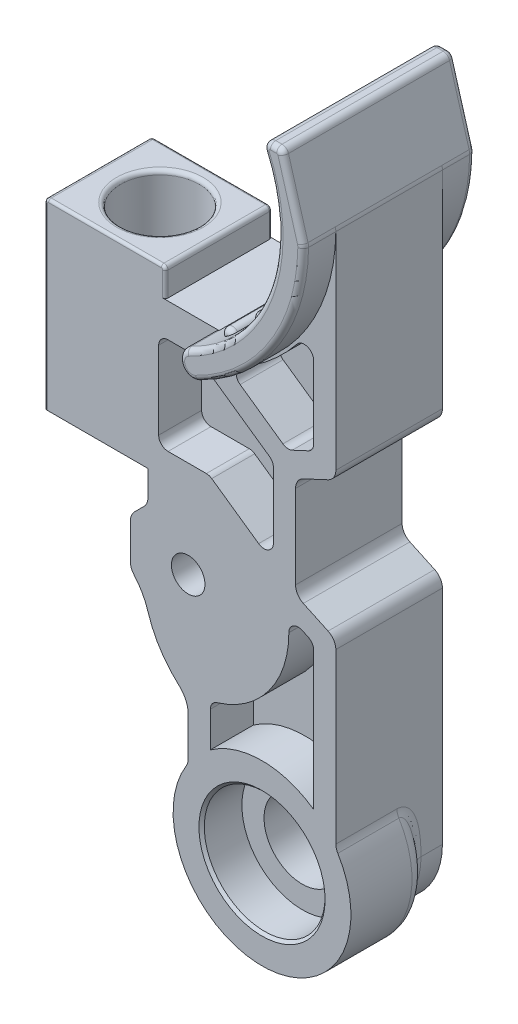
SolidWorks part; units mm, degrees
material "ABS"
ref_plane "Спереди" through (0, 0, 0) normal (0, 0, 1) x (1, 0, 0)
ref_plane "Сверху" through (0, 0, 0) normal (0, 1, 0) x (1, 0, 0)
ref_plane "Справа" through (0, 0, 0) normal (1, 0, 0) x (0, 0, -1)
sketch "Эскиз1" plane through (0, 0, 0) normal (0, 0, 1) x (1, 0, 0)
  line L0 (-9.8, 17.625) -> (-9.8, 14.125)
  line L1 (-5.5, 3.6933) -> (5.5, 3.6933) construction
  line L2 (-5.5, 3.6933) -> (-5.5, 17.1761) construction
  line L3 (-5.5, 17.1761) -> (5.5, 17.1761) construction
  line L4 (5.5, 3.6933) -> (5.5, 17.1761)
  line L5 (-9.8, 17.625) -> (-8.5, 18.925)
  line L6 (-8.5, 18.925) -> (-8.5, 21.225)
  line L7 (-8.5, 21.225) -> (-16.2, 21.225)
  line L8 (-16.2, 21.225) -> (-16.2, 34.875)
  line L9 (-16.2, 34.875) -> (-7.2, 34.875)
  line L10 (-7.2, 34.875) -> (-7.2, 32.775)
  line L11 (-7.2, 32.775) -> (-3.2, 32.775)
  line L12 (2.2662, 49.175) -> (3.9, 49.175)
  line L13 (5.5, 43.6525) -> (5.5, 27.4739)
  line L14 (5.5, 27.4739) -> (2.5, 26.075)
  line L15 (2.5, 26.075) -> (2.5, 18.575)
  line L16 (2.5, 18.575) -> (5.5, 17.1761)
  line L17 (3.9, 49.175) -> (5.5, 43.6525)
  line L18 (-5.5, 3.6933) -> (-5.5, 6.875)
  arc A0 (-5.5, 3.6933) -> (5.5, 3.6933) centre (0, 0) ccw
  arc A1 (-9.8, 14.125) -> (-8.5, 12.0004) centre (-13.2805, 10.5353) cw
  arc A2 (-8.5, 12.0004) -> (-6.1702, 8.3689) centre (-0.8511, 14.3444) ccw
  arc A3 (-6.1702, 8.3689) -> (-5.5, 6.875) centre (-7.5, 6.875) cw
  arc A4 (-3.2, 32.775) -> (2.2662, 49.175) centre (-8.5, 43.6525) ccw
  arc A5 (5.5, 43.6525) -> (-3.2, 30.6945) centre (-8.5, 43.6525) cw construction
  point P3 (-5.5, 15.875)
  point P15 (-9.8, 15.875)
  dimension "D1" = 13.25
  dimension "D2" = 22.5
  dimension "D6" = 2
  dimension "D7" = 8
  dimension "D8" = 5
  dimension "D9" = 13.5
  dimension "D17" = 41.5
  dimension "D22" = 14
  dimension "D23" = 1.9
  dimension "D26" = 25.2
  dimension "D3" = 11
  dimension "D4" = 15.3
  dimension "D5" = 3.5
  dimension "D10" = 14
  dimension "D11" = 45
  dimension "D12" = 11
  dimension "D13" = 3
  dimension "D14" = 2.3
  dimension "D15" = 18.7
  dimension "D16" = 13.65
  dimension "D18" = 4
  dimension "D19" = 2.1
  dimension "D20" = 9
  dimension "D21" = 55.8
  dimension "D24" = 1.6
  dimension "D25" = 7.5
  dimension "D27" = 25
  dimension "D28" = 25
extrude "Бобышка-Вытянуть1" add sketch "Эскиз1" along normal mid plane 7.94
sketch "Эскиз2" plane through (0, 0, 3.97) normal (0, 0, 1) x (1, 0, 0)
  line L0 (-3.85, 5.3915) -> (-3.85, 8.5588)
  line L1 (3.85, 5.3915) -> (3.85, 16.1249)
  line L2 (3.85, 16.1249) -> (2, 16.9876)
  line L3 (2, 16.9876) -> (2, 15.875)
  line L4 (2.5, 18.575) -> (5.5, 17.1761) construction
  line L5 (5.5, 3.6933) -> (5.5, 17.1761) construction
  line L6 (-5.5, 3.6933) -> (-5.5, 6.875) construction
  line L7 (-7.7, 23.075) -> (-7.7, 30.275)
  line L8 (-7.7, 30.275) -> (-4.7947, 30.275)
  line L9 (-4.7947, 30.275) -> (0.85, 26.3225)
  line L10 (0.85, 26.3225) -> (0.85, 19.7303)
  line L11 (0.85, 19.7303) -> (-3.9267, 23.075)
  line L12 (-3.9267, 23.075) -> (-7.7, 23.075)
  line L13 (-16.2, 21.225) -> (-16.2, 34.875) construction
  line L14 (2.5, 26.075) -> (2.5, 18.575) construction
  line L15 (-7.2, 32.775) -> (-3.2, 32.775) construction
  line L16 (-5.5, 17.1761) -> (5.5, 17.1761) construction
  line L18 (-2.5859, 30.7427) -> (1.8878, 27.6101)
  line L19 (1.8878, 27.6101) -> (3.85, 28.5251)
  line L20 (3.85, 28.5251) -> (3.85, 36.6441)
  line L21 (5.5, 43.6525) -> (5.5, 27.4739) construction
  line L22 (5.5, 27.4739) -> (2.5, 26.075) construction
  circle A0 centre (0, 0) radius 4.5
  arc A2 (2, 15.875) -> (-3.85, 8.5588) centre (-5.5, 15.875) cw
  arc A3 (-3.85, 5.3915) -> (3.85, 5.3915) centre (0, 0) cw
  arc A4 (-5.5, 3.6933) -> (5.5, 3.6933) centre (0, 0) ccw construction
  arc A5 (3.85, 36.6441) -> (-2.5859, 30.7427) centre (-8.5, 43.6525) cw
  point P21 (4, 17.8755)
  dimension "D1" = 9
  dimension "D2" = 7.5
  dimension "D15" = 14.2
  dimension "D3" = 1.65
  dimension "D4" = 1.65
  dimension "D5" = 1.65
  dimension "D6" = 8.5
  dimension "D7" = 1.65
  dimension "D8" = 2.5
  dimension "D9" = 35
  dimension "D10" = 5.4
  dimension "D11" = 29.7
  dimension "D12" = 1.65
  dimension "D13" = 1.65
  dimension "D14" = 1.65
extrude "Вырез-Вытянуть1" cut sketch "Эскиз2" against normal blind 3.2
fillet "Скругление1" radius 0.7 13 edges at (2, 16.9876, 2.37) (3.85, 36.6441, 2.37) (-2.5859, 30.7427, 2.37) (1.8878, 27.6101, 2.37) (3.85, 28.5251, 2.37) (-7.7, 30.275, 2.37) (-4.7947, 30.275, 2.37) (0.85, 26.3225, 2.37) (0.85, 19.7303, 2.37) (-3.9267, 23.075, 2.37) (-7.7, 23.075, 2.37) (3.85, 16.1249, 2.37) (-3.85, 8.5588, 2.37)
sketch "Эскиз4" plane through (0, 0, -3.97) normal (0, 0, -1) x (-1, 0, 0)
  line L0 (-3.4458, 16.3134) -> (-2.9958, 16.5232) construction
  line L1 (-2, 15.8888) -> (-2, 15.875) construction
  line L2 (3.85, 8.019) -> (3.85, 5.3915) construction
  line L3 (-3.85, 5.3915) -> (-3.85, 15.679) construction
  line L4 (5.0154, 30.275) -> (7, 30.275) construction
  line L5 (7.7, 29.575) -> (7.7, 23.775) construction
  line L6 (7, 23.075) -> (4.1474, 23.075) construction
  line L7 (3.7459, 22.9484) -> (0.2515, 20.5016) construction
  line L8 (-0.85, 21.075) -> (-0.85, 25.9581) construction
  line L9 (-0.5515, 26.5315) -> (4.6139, 30.1484) construction
  line L10 (-3.85, 28.971) -> (-3.85, 34.3634) construction
  line L11 (1.6305, 30.0736) -> (-1.5568, 27.8419) construction
  line L12 (-2.2541, 27.7809) -> (-3.4458, 28.3366) construction
  line L13 (-3.4458, 16.3134) -> (-2.9958, 16.5232)
  line L14 (-2, 15.8888) -> (-2, 15.875)
  line L15 (3.85, 8.019) -> (3.85, 3.2833)
  line L16 (-3.85, 3.2833) -> (-3.85, 15.679)
  line L17 (5.0154, 30.275) -> (7, 30.275)
  line L18 (7.7, 29.575) -> (7.7, 23.775)
  line L19 (7, 23.075) -> (4.1474, 23.075)
  line L20 (3.7459, 22.9484) -> (0.2515, 20.5016)
  line L21 (-0.85, 21.075) -> (-0.85, 25.9581)
  line L22 (-0.5515, 26.5315) -> (4.6139, 30.1484)
  line L23 (-3.85, 28.971) -> (-3.85, 34.3634)
  line L24 (1.6305, 30.0736) -> (-1.5568, 27.8419)
  line L25 (-2.2541, 27.7809) -> (-3.4458, 28.3366)
  arc A0 (-2, 15.8888) -> (-2.9958, 16.5232) centre (-2.7, 15.8888) ccw construction
  arc A1 (-2, 15.875) -> (3.3506, 8.6896) centre (5.5, 15.875) ccw construction
  arc A2 (3.85, 8.019) -> (3.3506, 8.6896) centre (3.15, 8.019) ccw construction
  arc A4 (-3.4458, 16.3134) -> (-3.85, 15.679) centre (-3.15, 15.679) ccw construction
  arc A5 (7.7, 29.575) -> (7, 30.275) centre (7, 29.575) ccw construction
  arc A6 (7, 23.075) -> (7.7, 23.775) centre (7, 23.775) ccw construction
  arc A7 (4.1474, 23.075) -> (3.7459, 22.9484) centre (4.1474, 22.375) ccw construction
  arc A8 (-0.85, 21.075) -> (0.2515, 20.5016) centre (-0.15, 21.075) ccw construction
  arc A9 (-0.5515, 26.5315) -> (-0.85, 25.9581) centre (-0.15, 25.9581) ccw construction
  arc A10 (5.0154, 30.275) -> (4.6139, 30.1484) centre (5.0154, 29.575) ccw construction
  arc A11 (-2.6027, 34.7998) -> (-3.85, 34.3634) centre (-3.15, 34.3634) ccw construction
  arc A12 (-2.6027, 34.7998) -> (1.5705, 31.258) centre (8.5, 43.6525) ccw construction
  arc A13 (1.6305, 30.0736) -> (1.5705, 31.258) centre (1.229, 30.647) ccw construction
  arc A14 (-2.2541, 27.7809) -> (-1.5568, 27.8419) centre (-1.9583, 28.4153) ccw construction
  arc A15 (-3.85, 28.971) -> (-3.4458, 28.3366) centre (-3.15, 28.971) ccw construction
  arc A16 (-2, 15.8888) -> (-2.9958, 16.5232) centre (-2.7, 15.8888) ccw
  arc A17 (-2, 15.875) -> (3.3506, 8.6896) centre (5.5, 15.875) ccw
  arc A18 (3.85, 8.019) -> (3.3506, 8.6896) centre (3.15, 8.019) ccw
  arc A19 (2.6654, 2.7782) -> (-2.6654, 2.7782) centre (0, 0) ccw
  arc A20 (-3.4458, 16.3134) -> (-3.85, 15.679) centre (-3.15, 15.679) ccw
  arc A21 (7.7, 29.575) -> (7, 30.275) centre (7, 29.575) ccw
  arc A22 (7, 23.075) -> (7.7, 23.775) centre (7, 23.775) ccw
  arc A23 (4.1474, 23.075) -> (3.7459, 22.9484) centre (4.1474, 22.375) ccw
  arc A24 (-0.85, 21.075) -> (0.2515, 20.5016) centre (-0.15, 21.075) ccw
  arc A25 (-0.5515, 26.5315) -> (-0.85, 25.9581) centre (-0.15, 25.9581) ccw
  arc A26 (5.0154, 30.275) -> (4.6139, 30.1484) centre (5.0154, 29.575) ccw
  arc A27 (-2.6027, 34.7998) -> (-3.85, 34.3634) centre (-3.15, 34.3634) ccw
  arc A28 (-2.6027, 34.7998) -> (1.5705, 31.258) centre (8.5, 43.6525) ccw
  arc A29 (1.6305, 30.0736) -> (1.5705, 31.258) centre (1.229, 30.647) ccw
  arc A30 (-2.2541, 27.7809) -> (-1.5568, 27.8419) centre (-1.9583, 28.4153) ccw
  arc A31 (-3.85, 28.971) -> (-3.4458, 28.3366) centre (-3.15, 28.971) ccw
  arc A32 (3.85, 3.2833) -> (2.6654, 2.7782) centre (3.15, 3.2833) cw
  arc A33 (-2.6654, 2.7782) -> (-3.85, 3.2833) centre (-3.15, 3.2833) cw
  dimension "D1" = 3.85
  dimension "D2" = 0.7
extrude "Вырез-Вытянуть2" cut sketch "Эскиз4" against normal blind 3.2
sketch "Эскиз5" plane through (0, 0, 0.77) normal (0, 0, 1) x (1, 0, 0)
  circle A1 centre (0, 0) radius 4.5
  circle A2 centre (0, 0) radius 4.5
  dimension "D1" = 0
extrude "Бобышка-Вытянуть2" add sketch "Эскиз5" along normal blind 0.2
sketch "Эскиз6" plane through (0, 0, 0.97) normal (0, 0, 1) x (1, 0, 0)
  circle A0 centre (0, 0) radius 2.85
  dimension "D1" = 5.7
extrude "Вырез-Вытянуть3" cut sketch "Эскиз6" against normal through all
sketch "Эскиз7" plane through (0, 0, -0.77) normal (0, 0, -1) x (-1, 0, 0)
  line L0 (3.85, 5.3915) -> (3.85, 8.5588) construction
  line L7 (-3.85, 15.679) -> (-3.85, 3.2833)
  line L8 (3.85, 3.2833) -> (3.85, 8.019)
  line L9 (-2, 15.875) -> (-2, 15.8888)
  line L10 (-2.9958, 16.5232) -> (-3.4458, 16.3134)
  line L11 (-3.85, 5.3915) -> (-3.85, 3.2833)
  line L12 (3.85, 3.2833) -> (3.85, 5.3915)
  arc A0 (-3.85, 5.3915) -> (3.85, 5.3915) centre (0, 0) cw
  arc A9 (-3.4458, 16.3134) -> (-3.85, 15.679) centre (-3.15, 15.679) ccw
  arc A10 (-3.85, 3.2833) -> (-2.6654, 2.7782) centre (-3.15, 3.2833) ccw
  arc A11 (2.6654, 2.7782) -> (-2.6654, 2.7782) centre (0, 0) ccw
  arc A12 (2.6654, 2.7782) -> (3.85, 3.2833) centre (3.15, 3.2833) ccw
  arc A13 (3.85, 8.019) -> (3.3506, 8.6896) centre (3.15, 8.019) ccw
  arc A14 (-2, 15.875) -> (3.3506, 8.6896) centre (5.5, 15.875) ccw
  arc A15 (-2, 15.8888) -> (-2.9958, 16.5232) centre (-2.7, 15.8888) ccw
  arc A17 (-3.85, 3.2833) -> (-2.6654, 2.7782) centre (-3.15, 3.2833) ccw
  arc A18 (2.6654, 2.7782) -> (-2.6654, 2.7782) centre (0, 0) ccw
  arc A19 (2.6654, 2.7782) -> (3.85, 3.2833) centre (3.15, 3.2833) ccw
  dimension "D1" = 0
extrude "Бобышка-Вытянуть3" add sketch "Эскиз7" along normal offset from surface (0.9 mm away) 2.3 up to face at (2.85, 0, -3.97)
fillet "Скругление2" radius 0.5 1 edges at (0, 6.625, -1.67)
fillet "Скругление3" radius 0.5 1 edges at (0, 6.625, -0.77)
sketch "Эскиз8" plane through (0, 0, -3.97) normal (0, 0, -1) x (-1, 0, 0)
  line L0 (-5.5, 3.6933) -> (-5.5, 0)
  line L1 (5.5, 0) -> (5.5, 3.6933)
  arc A0 (-5.5, 0) -> (5.5, 0) centre (0, 0) ccw
  arc A3 (-5.5, 3.6933) -> (5.5, 3.6933) centre (0, 0) ccw
  arc A4 (-5.5, 3.6933) -> (5.5, 3.6933) centre (0, 0) ccw
  dimension "D1" = 0
extrude "Вырез-Вытянуть4" cut sketch "Эскиз8" against normal offset from surface (2.39 mm away) 5.55 up to face at (4.5, 0, 3.97)
fillet "Скругление4" radius 1 1 edges at (0, -6.625, -1.58)
sketch "Эскиз9" plane through (0, 0, 0) normal (0, 0, 1) x (1, 0, 0)
  line L3 (-9.8, 17.625) -> (-9.8, 14.125) construction
  line L4 (-5.5, 10.675) -> (-7.9599, 10.675)
  line L5 (-5.5, 21.075) -> (-8.5, 21.075)
  line L6 (-8.5, 18.925) -> (-8.5, 21.225) construction
  line L19 (-9.8, 17.625) -> (-9.8, 14.125)
  line L20 (-8.5, 18.925) -> (-9.8, 17.625)
  line L21 (-8.5, 21.225) -> (-8.5, 18.925)
  line L22 (-9.8, 17.625) -> (-9.8, 14.125)
  line L23 (-8.5, 18.925) -> (-9.8, 17.625)
  line L24 (-8.5, 21.075) -> (-8.5, 18.925)
  arc A0 (-5.5, 10.675) -> (-5.5, 21.075) centre (-5.5, 15.875) ccw
  arc A1 (-8.5, 12.0004) -> (-6.1702, 8.3689) centre (-0.8511, 14.3444) ccw construction
  arc A7 (-8.5, 12.0004) -> (-6.1702, 8.3689) centre (-0.8511, 14.3444) ccw
  arc A8 (-8.5, 12.0004) -> (-9.8, 14.125) centre (-13.2805, 10.5353) ccw
  arc A9 (-8.5, 12.0004) -> (-7.9599, 10.675) centre (-0.8511, 14.3444) ccw
  arc A10 (-8.5, 12.0004) -> (-9.8, 14.125) centre (-13.2805, 10.5353) ccw
  dimension "D1" = 9.5
  dimension "D2" = 0
extrude "Вырез-Вытянуть5" cut sketch "Эскиз9" against normal mid plane 4.35
sketch "Эскиз10" plane through (0, 0, 0) normal (0, 0, 1) x (1, 0, 0)
  line L0 (-8.5, 43.6525) -> (-8.5, 34.875) construction
  line L1 (-16.2, 34.875) -> (-7.2, 34.875) construction
  line L2 (-8.5, 43.6525) -> (-1.5597, 33.7408) construction
  line L3 (-8.5, 43.6525) -> (-1.5597, 33.7408) construction
  line L4 (-8.5, 43.6525) -> (0.7691, 35.8748) construction
  arc A0 (-1.9331, 33.4895) -> (-1.1959, 34.0057) centre (-1.5597, 33.7408) cw
  arc A1 (-3.2, 32.775) -> (2.2662, 49.175) centre (-8.5, 43.6525) ccw construction
  arc A2 (-1.9331, 33.4895) -> (-1.1959, 34.0057) centre (-8.5, 43.6525) ccw
  arc A3 (0.4735, 35.5354) -> (1.052, 36.2249) centre (0.7691, 35.8748) cw
  arc A4 (0.4735, 35.5354) -> (1.052, 36.2249) centre (-8.5, 43.6525) ccw
  arc A5 (2.2686, 38.1345) -> (2.6489, 38.9502) centre (2.4663, 38.5388) cw
  arc A6 (2.2686, 38.1345) -> (2.6489, 38.9502) centre (-8.5, 43.6525) ccw
  arc A7 (3.3298, 41.1096) -> (3.4861, 41.996) centre (3.4162, 41.5514) cw
  arc A8 (3.3298, 41.1096) -> (3.4861, 41.996) centre (-8.5, 43.6525) ccw
  arc A9 (3.5848, 44.2581) -> (3.5064, 45.1546) centre (3.554, 44.7071) cw
  arc A10 (3.5848, 44.2581) -> (3.5064, 45.1546) centre (-8.5, 43.6525) ccw
  arc A11 (3.0163, 47.3652) -> (2.7085, 48.2109) centre (2.8703, 47.7909) cw
  arc A12 (3.0163, 47.3652) -> (2.7085, 48.2109) centre (-8.5, 43.6525) ccw
  dimension "D1" = 0.9
  dimension "D2" = 35
  dimension "D4" = 15
  dimension "D3" = 6
sketch "Эскиз11" plane through (0, 0, 0) normal (0, 0, 1) x (1, 0, 0)
  line L0 (2.2662, 49.175) -> (3.9, 49.175)
  line L1 (3.9, 49.175) -> (5.5, 43.6525)
  arc A0 (2.2662, 49.175) -> (-3.2, 32.775) centre (-8.5, 43.6525) cw
  arc A1 (5.5, 43.6525) -> (-2.3678, 31.067) centre (-8.5, 43.6525) cw
  arc A2 (-3.2, 32.775) -> (-2.3678, 31.067) centre (-2.7839, 31.921) ccw
extrude "Бобышка-Вытянуть4" add sketch "Эскиз11" along normal mid plane 12.8
extrude "Бобышка-Вытянуть5" add sketch "Эскиз10" along normal mid plane 10
sketch "Эскиз12" plane through (0, 0, -3.97) normal (0, 0, -1) x (-1, 0, 0)
  circle A0 centre (5.5, 15.875) radius 1.7
  dimension "D1" = 3.4
extrude "Вырез-Вытянуть6" cut sketch "Эскиз12" against normal up to surface (1.795 mm away) up to face at (-7.3444, 15.7807, -2.175)
sketch "Эскиз13" plane through (-16.2, 0, 0) normal (-1, 0, 0) x (0, 0, 1)
  line L0 (3.97, 21.225) -> (-3.97, 21.225) construction
  line L1 (-2.175, 21.225) -> (-2.175, 24.225)
  line L2 (-2.175, 24.225) -> (2.175, 24.225)
  line L3 (2.175, 24.225) -> (2.175, 21.225)
  line L4 (-2.175, 21.075) -> (-2.175, 18.925) construction
  line L5 (2.175, 21.075) -> (2.175, 18.925) construction
  line L6 (-2.175, 21.225) -> (2.175, 21.225)
  dimension "D1" = 3
extrude "Вырез-Вытянуть7" cut sketch "Эскиз13" against normal blind 7.8
sketch "Эскиз14" plane through (0, 34.875, 0) normal (0, 1, 0) x (1, 0, 0)
  line L0 (-8.5, 0) -> (-16.2, 0) construction
  line L4 (-16.2, -3.97) -> (-16.2, 3.97) construction
  circle A0 centre (-11.575, 0) radius 2.925
  dimension "D1" = 5.85
  dimension "D2" = 1.7
extrude "Вырез-Вытянуть8" cut sketch "Эскиз14" against normal up to surface (10.65 mm away) up to face at (-12.3, 24.225, 0)
fillet "Скругление5" radius 0.5 2 edges at (3.9, 49.175, 0) (2.2662, 49.175, 0)
fillet "Скругление7" radius 1 3 edges at (5.5, 43.6525, 5.185) (5.5, 43.6525, -5.185) (5.5, 43.6525, 0)
fillet "Скругление8" radius 0.4 12 edges at (2.4473, 47.637, -5) (3.1056, 44.6679, -5) (2.9729, 41.6295, -5) (2.0584, 38.729, -5) (0.4244, 36.1641, -5) (-1.8179, 34.1094, -5) (-1.8179, 34.1094, 5) (0.4244, 36.1641, 5) (2.4473, 47.637, 5) (3.1056, 44.6679, 5) (2.9729, 41.6295, 5) (2.0584, 38.729, 5)
fillet "Скругление9" radius 0.4 16 edges at (2.6376, 48.9492, -6.4) (3.29, 49.175, -6.4) (3.8247, 49.0747, -6.4) (4.7322, 46.3028, -6.4) (5.4901, 43.6484, -6.4) (3.3313, 36.1678, -6.4) (-3.6379, 31.5049, -6.4) (2.6376, 48.9492, 6.4) (3.29, 49.175, 6.4) (3.8247, 49.0747, 6.4) (4.7322, 46.3028, 6.4) (5.4901, 43.6484, 6.4) (3.3313, 36.1678, 6.4) (-3.6379, 31.5049, 6.4) (2.851, 39.4614, -6.4) (2.851, 39.4614, 6.4)
fillet "Скругление10" radius 1 15 edges at (5.5, 17.1761, 0) (2.5, 18.575, 0) (2.5, 26.075, 0) (5.5, 27.4739, 0) (-5.5, 3.6933, 1.695) (-5.5, 3.3808, -1.1363) (-5.5, 0.5896, -1.58) (5.5, 3.5264, -0.9981) (-8.5, 18.925, -3.0725) (-8.5, 18.925, 3.0725) (-9.8, 17.625, 3.0725) (-9.8, 14.125, 3.0725) (-9.8, 17.625, -3.0725) (-9.8, 14.125, -3.0725) (5.5, 3.6933, 1.695)
hole_wizard "Отверстие обработанное метчиком M31" positions "Эскиз15" profile "Эскиз16" tap size "M3" standard "GOST" end condition up to next
sketch "Эскиз15" plane through (0, 0, 3.97) normal (0, 0, 1) x (1, 0, 0)
  point P0 (-5.5, 15.875)
cosmetic thread "Отверстие резьбы1" parameters "D2"=3
sketch "Эскиз16" plane through (-5.5, 15.875, 3.97) normal (1, 0, 0) x (0, -1, 0)
  line L0 (0, 0) -> (0, 1.795)
  line L1 (0, 1.795) -> (1.25, 1.795)
  line L2 (1.25, 1.795) -> (1.25, 0)
  line L5 (1.25, 0) -> (0, 0)
  line L11 (0, -6.35) -> (0, 107.95) construction
  dimension "Диаметр проходного сверла" = 2.5
  dimension "Глубина проходного сверла" = 1.795
fillet "Скругление11" radius 0.3 3 edges at (-14.5, 34.875, 0) (-7.2, 34.875, 0) (-16.2, 34.875, 0)
chamfer "Фаска1" distance 0.2 angle 45 1 edges at (4.5, 0, 3.97)
fillet "Скругление12" radius 0.2 10 edges at (-7.2, 33.675, -3.97) (-7.2879, 34.7871, -3.97) (-11.7, 34.875, -3.97) (-16.1121, 34.7871, -3.97) (-7.2, 33.675, 3.97) (-7.2879, 34.7871, 3.97) (-11.7, 34.875, 3.97) (-16.1121, 34.7871, 3.97) (-16.2, 27.9, -3.97) (-16.2, 27.9, 3.97)
equation "\"D3@Эскиз2\"=\"D4@Эскиз2\""
equation "\"D5@Эскиз2\"=\"D4@Эскиз2\""
equation "\"D7@Эскиз2\"=\"D4@Эскиз2\""
equation "\"D13@Эскиз2\"=\"D4@Эскиз2\""
equation "\"D14@Эскиз2\"=\"D4@Эскиз2\""
equation "\"D12@Эскиз2\"=\"D4@Эскиз2\""
